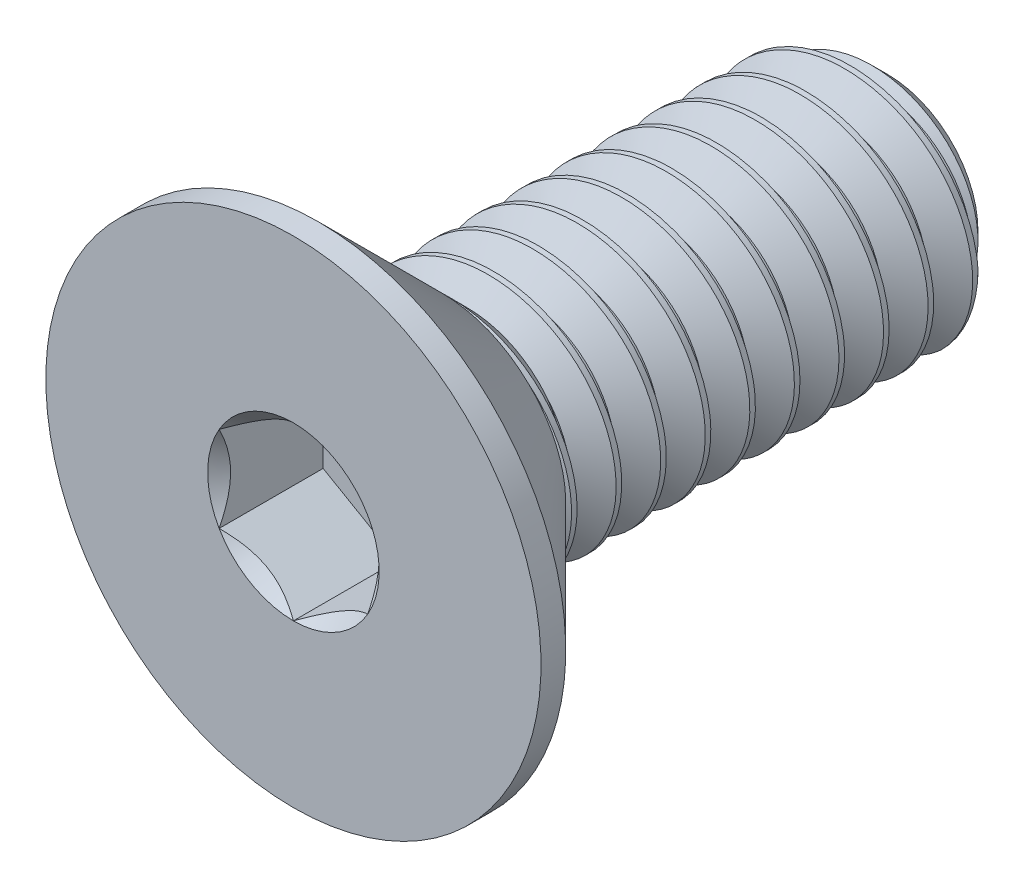
SolidWorks part; units mm, degrees
ref_plane "Front" through (0, 0, 0) normal (0, 0, 1) x (1, 0, 0)
ref_plane "Top" through (0, 0, 0) normal (0, 1, 0) x (1, 0, 0)
ref_plane "Right" through (0, 0, 0) normal (1, 0, 0) x (0, 0, -1)
sketch "Sketch1" plane through (0, 0, 0) normal (1, 0, 0) x (0, 0, -1)
  line L0 (0, 2.5) -> (0.25, 2.5) construction
  line L1 (0.25, 2.5) -> (1.5, 1.25) construction
  line L2 (0, 1.25) -> (6, 1.25)
  line L3 (6, 1.25) -> (6, 0)
  line L4 (6, 0) -> (0, 0)
  line L5 (0, 0) -> (0, 2.5) construction
  line L6 (0, 2.5) -> (0, -2.5) construction
  line L7 (6, 1.25) -> (6, -1.25) construction
  line L8 (0, -2.5) -> (0.25, -2.5) construction
  line L9 (0.25, -2.5) -> (1.5, -1.25) construction
  line L11 (0, 1.25) -> (0, 0)
  line L12 (1.5, 1.25) -> (1.5, 0) construction
revolve "Revolve1" add sketch "Sketch1" angle 360 mid plane about L4
sketch "Sketch3" plane through (0, 0, -6) normal (0, 0, -1) x (-1, 0, 0)
  circle A0 centre (0, 0) radius 1.25
curve "Helix/Spiral1" pitch 0.45 height 6 radius 1.25 centre (0, 0, -6) axis (0, 0, 1) start towards (0, 1, 0)
sketch "Sketch2" plane through (0, 0, 0) normal (1, 0, 0) x (0, 0, -1)
  line L0 (6, 1.25) -> (6.3938, 1.25)
  line L1 (6.3938, 1.25) -> (6.225, 0.9577)
  line L2 (6.225, 0.9577) -> (6.1687, 0.9577)
  line L3 (6.1687, 0.9577) -> (6, 1.25)
  line L4 (6.0844, 1.1039) -> (6.3094, 1.1039) construction
  dimension "D1" = 60
  dimension "D2" = 0.0563
  dimension "D3" = 0.225
chamfer "Chamfer1" distance 0.3375 angle 45 1 edges at (0, 1.25, -6)
sweep "Cut-Sweep1" cut profiles "Sketch2" path "Helix/Spiral1" align with end faces yes
sketch "Sketch7" plane through (0, 0, 0) normal (1, 0, 0) x (0, 0, -1)
  line L0 (0, 2.5) -> (0.25, 2.5) construction
  line L1 (0.25, 2.5) -> (1.5, 1.25) construction
  line L2 (0, 2.5) -> (0.25, 2.5)
  line L3 (0.25, 2.5) -> (1.5, 1.25)
  line L4 (1.5, 1.25) -> (1.5, 0) construction
  line L5 (1.5, 1.25) -> (1.5, 0)
  line L7 (0, 0) -> (0, 2.5) construction
  line L8 (0, 0) -> (0, 2.5)
  line L9 (0, 0) -> (1.5, 0)
  line L10 (2.75, 0) -> (-2.75, 0) construction
revolve "Revolve2" add sketch "Sketch7" angle 360 mid plane about L9
ref_plane "Plane1" through (0, 0, -1.5) normal (0, 0, 1) x (1, 0, 0)
sketch "Sketch8" plane through (0, 0, -1.5) normal (0, 0, 1) x (1, 0, 0)
  circle A0 centre (0, 0) radius 1.25
extrude "Boss-Extrude1" add sketch "Sketch8" against normal through all draft 45
sketch "Sketch5" plane through (0, 0, 0) normal (0, 0, 1) x (1, 0, 0)
  line L1 (0.75, -0.433) -> (0.75, 0.433)
  line L2 (0.75, 0.433) -> (0, 0.866)
  line L3 (0, 0.866) -> (-0.75, 0.433)
  line L4 (-0.75, 0.433) -> (-0.75, -0.433)
  line L5 (-0.75, -0.433) -> (0, -0.866)
  line L6 (0, -0.866) -> (0.75, -0.433)
  circle A0 centre (0, 0) radius 0.75 construction
  dimension "Hex" = 1.5
extrude "Cut-Extrude2" cut sketch "Sketch5" against normal blind 1.05
sketch "Sketch6" plane through (0, 0, 0) normal (0, 0, 1) x (1, 0, 0)
  circle A0 centre (0, 0) radius 0.866
extrude "Cut-Extrude3" cut sketch "Sketch6" against normal blind 1.05 draft 45
sketch "Sketch9" [suppressed] plane through (0, 0, -1.5) normal (0, 0, 1) x (1, 0, 0)
  circle A1 centre (0, 0) radius 1.25
  circle A2 centre (0, 0) radius 1.25
  point P0 (0, 1.25)
  dimension "D1" = 0
extrude "Boss-Extrude2" [suppressed] add sketch "Sketch9" against normal offset from surface (3.5 mm away) 26 up to face at (0, 0.9125, -6)
fillet "Fillet1" [suppressed] radius 0.25
sketch "Sketch10" plane through (0, 0, 0) normal (1, 0, 0) x (0, 0, -1)
  line L0 (6, 1.25) -> (6, -1.25) construction
  point P0 (5.325, -1.25)
  dimension "D1" = 0.675
equation "\"D3@Helix/Spiral1\" = \"Lg@Sketch1\""
equation "\"D2@Sketch2\" = \"D4@Helix/Spiral1\" * .125"
equation "\"D3@Sketch2\" = \"D4@Helix/Spiral1\" * .5"
equation "\"D1@Chamfer1\" = \"D4@Helix/Spiral1\" * .75"
equation "\"D1@Cut-Extrude2\" = \"Head Ht@Sketch1\" * .7"
equation "\"D1@Sketch10\" = \"D4@Helix/Spiral1\" * 1.5"
equation "\"D1@Cut-Extrude3\" = \"D1@Cut-Extrude2\""
equation "\"D1@Fillet1\" = \"Dia@Sketch1\" * .1"
